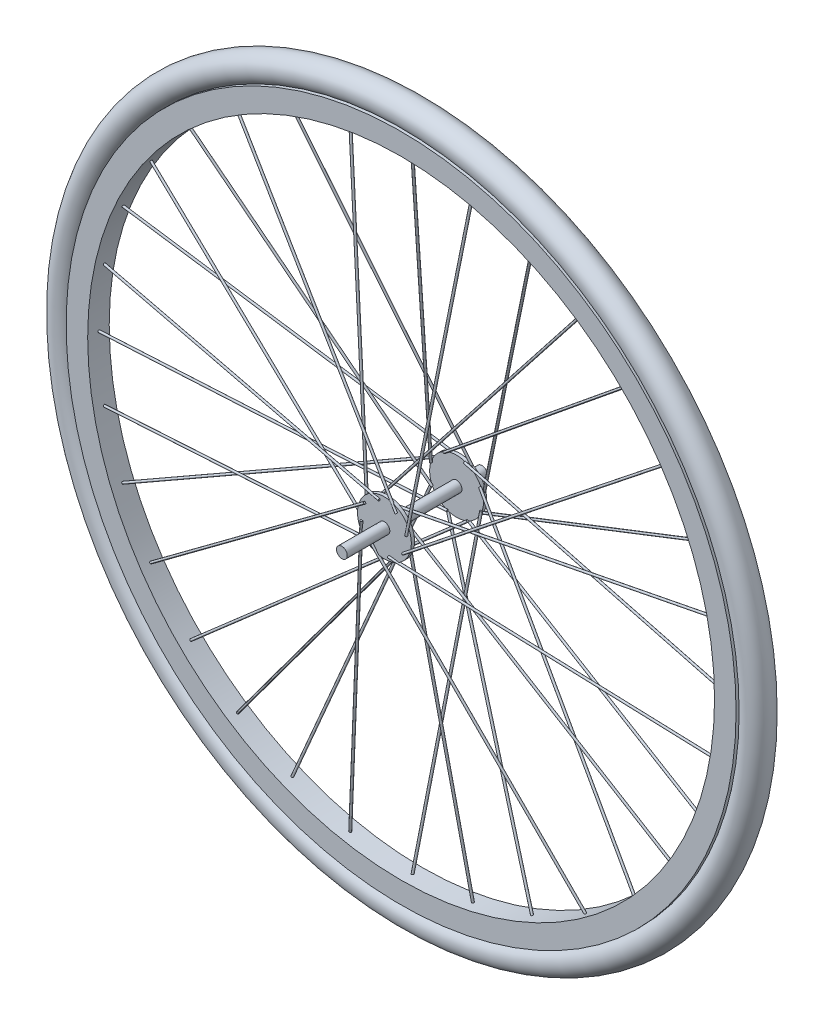
SolidWorks part; units mm, degrees
material "6061-T6 (SS)"
ref_plane "Alzado" through (0, 0, 0) normal (0, 0, 1) x (1, 0, 0)
ref_plane "Planta" through (0, 0, 0) normal (0, 1, 0) x (1, 0, 0)
ref_plane "Vista lateral" through (0, 0, 0) normal (1, 0, 0) x (0, 0, -1)
sketch "Sk_Llanta" plane through (0, 0, 0) normal (0, 0, 1) x (1, 0, 0)
  circle A0 centre (-425.1, 65) radius 311
  circle A1 centre (-425.1, 65) radius 291
  dimension "D1" = 622
  dimension "D2" = 582
extrude "Llanta" add sketch "Sk_Llanta" along normal mid plane 20
sketch "Sk_Cubierta" plane through (0, 0, 0) normal (0, 0, 1) x (1, 0, 0)
  circle A0 centre (-425.1, 65) radius 321.5
  dimension "D1" = 643
sweep "Cubierta" add path "Sk_Cubierta" circular profile diameter 25 parameters "D3"=25
sketch3d "Sk_Eje"
  line L0 (-425.1, 65, -65) -> (-425.1, 65, 65)
  dimension "D1" = 130
sweep "Eje" add path "Sk_Eje" circular profile diameter 10 parameters "D3"=10
sketch3d "Sk_Buje"
  line L0 (-425.1, 65, -50) -> (-425.1, 65, 50)
  dimension "D1" = 100
sweep "Buje" [suppressed] add path "Sk_Buje" circular profile diameter 30 parameters "D3"=30
sketch3d "Sk_Pestana_izq"
  line L0 (-425.1, 65, -44.5) -> (-425.1, 65, -41.5)
  dimension "D1" = 3
sweep "Pestana_izq" add path "Sk_Pestana_izq" circular profile diameter 50 parameters "D3"=50
sketch3d "Sk_Pestana_dcha"
  line L0 (-425.1, 65, 22.5) -> (-425.1, 65, 25.5)
  dimension "D1" = 3
sweep "Pestana_dcha" add path "Sk_Pestana_dcha" circular profile diameter 50 parameters "D3"=50
sketch3d "Sk_Radio_izq_a"
  line L0 (-403.8575, 65.2425, -45) -> (-312.5911, 336.6206, 0)
  dimension "D1" = 289.8286
sweep "Radio_izq_a" add path "Sk_Radio_izq_a" circular profile diameter 2 parameters "D3"=2
sketch3d "Sk_Radio_izq_b"
  line L0 (-402.9187, 75.8162, -41) -> (-217.2106, -142.8894, 0)
  dimension "D1" = 289.8286
sweep "Radio_izq_b" add path "Sk_Radio_izq_b" circular profile diameter 2 parameters "D3"=2
sketch3d "Sk_Radio_dcha_a"
  line L0 (-404.3477, 69.2527, 26) -> (-367.7434, 353.3509, 0)
  dimension "D1" = 287.6241
sweep "Radio_dcha_a" add path "Sk_Radio_dcha_a" circular profile diameter 2 parameters "D3"=2
sketch3d "Sk_Radio_dcha_b"
  line L0 (-408.5094, 75.7967, 22) -> (-180.6479, -98.3376, 0)
  dimension "D1" = 287.6241
sweep "Radio_dcha_b" add path "Sk_Radio_dcha_b" circular profile diameter 2 parameters "D3"=2
ref_axis "Eje_buje" through (-425.1, 65, 25.5) along (0, 0, 1)
sketch3d "Sk_Pinon_1"
  line L0 (-425.1, 65, 26.5) -> (-425.1, 65, 28.5)
  dimension "D1" = 2
sweep "Pinon_1" [suppressed] add path "Sk_Pinon_1" circular profile diameter 120 parameters "D3"=120
sketch "Sk_Dientes_pinon_1" plane through (0, 0, 0) normal (0, 0, 1) x (1, 0, 0)
  line L0 (-367.1, 62.46) -> (-362.1, 64)
  line L1 (-362.1, 64) -> (-362.1, 66)
  line L2 (-362.1, 66) -> (-367.1, 67.54)
  line L3 (-367.1, 67.54) -> (-367.1, 62.46)
extrude "Dientes_pinon_1" [suppressed] add sketch "Sk_Dientes_pinon_1" along normal blind 2 from offset 26.5
pattern_circular "Matriz_Dientes_pinon_1" [suppressed] count 30 over 360 about axis through (-425.1, 65, 25.5) along (0, 0, 1) of bodies 111
sketch3d "Sk_Pinon_2"
  line L0 (-425.1, 65, 30.5) -> (-425.1, 65, 32.5)
  dimension "D1" = 2
sweep "Pinon_2" [suppressed] add path "Sk_Pinon_2" circular profile diameter 110 parameters "D3"=110
sketch "Sk_Dientes_pinon_2" plane through (0, 0, 0) normal (0, 0, 1) x (1, 0, 0)
  line L0 (-372.1, 62.46) -> (-367.1, 64)
  line L1 (-367.1, 64) -> (-367.1, 66)
  line L2 (-367.1, 66) -> (-372.1, 67.54)
  line L3 (-372.1, 67.54) -> (-372.1, 62.46)
extrude "Dientes_pinon_2" [suppressed] add sketch "Sk_Dientes_pinon_2" along normal blind 2 from offset 30.5
pattern_circular "Matriz_Dientes_pinon_2" [suppressed] count 27 over 360 about axis through (-425.1, 65, 25.5) along (0, 0, 1) of bodies 111
sketch3d "Sk_Pinon_3"
  line L0 (-425.1, 65, 34.5) -> (-425.1, 65, 36.5)
  dimension "D1" = 2
sweep "Pinon_3" [suppressed] add path "Sk_Pinon_3" circular profile diameter 100 parameters "D3"=100
sketch "Sk_Dientes_pinon_3" plane through (0, 0, 0) normal (0, 0, 1) x (1, 0, 0)
  line L0 (-377.1, 62.46) -> (-372.1, 64)
  line L1 (-372.1, 64) -> (-372.1, 66)
  line L2 (-372.1, 66) -> (-377.1, 67.54)
  line L3 (-377.1, 67.54) -> (-377.1, 62.46)
extrude "Dientes_pinon_3" [suppressed] add sketch "Sk_Dientes_pinon_3" along normal blind 2 from offset 34.5
pattern_circular "Matriz_Dientes_pinon_3" [suppressed] count 25 over 360 about axis through (-425.1, 65, 25.5) along (0, 0, 1) of bodies 111
sketch3d "Sk_Pinon_4"
  line L0 (-425.1, 65, 38.5) -> (-425.1, 65, 40.5)
  dimension "D1" = 2
sweep "Pinon_4" [suppressed] add path "Sk_Pinon_4" circular profile diameter 90 parameters "D3"=90
sketch "Sk_Dientes_pinon_4" plane through (0, 0, 0) normal (0, 0, 1) x (1, 0, 0)
  line L0 (-382.1, 62.46) -> (-377.1, 64)
  line L1 (-377.1, 64) -> (-377.1, 66)
  line L2 (-377.1, 66) -> (-382.1, 67.54)
  line L3 (-382.1, 67.54) -> (-382.1, 62.46)
extrude "Dientes_pinon_4" [suppressed] add sketch "Sk_Dientes_pinon_4" along normal blind 2 from offset 38.5
pattern_circular "Matriz_Dientes_pinon_4" [suppressed] count 22 over 360 about axis through (-425.1, 65, 25.5) along (0, 0, 1) of bodies 111
sketch3d "Sk_Pinon_5"
  line L0 (-425.1, 65, 42.5) -> (-425.1, 65, 44.5)
  dimension "D1" = 2
sweep "Pinon_5" [suppressed] add path "Sk_Pinon_5" circular profile diameter 82 parameters "D3"=82
sketch "Sk_Dientes_pinon_5" plane through (0, 0, 0) normal (0, 0, 1) x (1, 0, 0)
  line L0 (-386.1, 62.46) -> (-381.1, 64)
  line L1 (-381.1, 64) -> (-381.1, 66)
  line L2 (-381.1, 66) -> (-386.1, 67.54)
  line L3 (-386.1, 67.54) -> (-386.1, 62.46)
extrude "Dientes_pinon_5" [suppressed] add sketch "Sk_Dientes_pinon_5" along normal blind 2 from offset 42.5
pattern_circular "Matriz_Dientes_pinon_5" [suppressed] count 20 over 360 about axis through (-425.1, 65, 25.5) along (0, 0, 1) of bodies 111
sketch3d "Sk_Pinon_6"
  line L0 (-425.1, 65, 46.5) -> (-425.1, 65, 48.5)
  dimension "D1" = 2
sweep "Pinon_6" [suppressed] add path "Sk_Pinon_6" circular profile diameter 74 parameters "D3"=74
sketch "Sk_Dientes_pinon_6" plane through (0, 0, 0) normal (0, 0, 1) x (1, 0, 0)
  line L0 (-390.1, 62.46) -> (-385.1, 64)
  line L1 (-385.1, 64) -> (-385.1, 66)
  line L2 (-385.1, 66) -> (-390.1, 67.54)
  line L3 (-390.1, 67.54) -> (-390.1, 62.46)
extrude "Dientes_pinon_6" [suppressed] add sketch "Sk_Dientes_pinon_6" along normal blind 2 from offset 46.5
pattern_circular "Matriz_Dientes_pinon_6" [suppressed] count 18 over 360 about axis through (-425.1, 65, 25.5) along (0, 0, 1) of bodies 111
sketch3d "Sk_Pinon_7"
  line L0 (-425.1, 65, 50.5) -> (-425.1, 65, 52.5)
  dimension "D1" = 2
sweep "Pinon_7" [suppressed] add path "Sk_Pinon_7" circular profile diameter 66 parameters "D3"=66
sketch "Sk_Dientes_pinon_7" plane through (0, 0, 0) normal (0, 0, 1) x (1, 0, 0)
  line L0 (-394.1, 62.46) -> (-389.1, 64)
  line L1 (-389.1, 64) -> (-389.1, 66)
  line L2 (-389.1, 66) -> (-394.1, 67.54)
  line L3 (-394.1, 67.54) -> (-394.1, 62.46)
extrude "Dientes_pinon_7" [suppressed] add sketch "Sk_Dientes_pinon_7" along normal blind 2 from offset 50.5
pattern_circular "Matriz_Dientes_pinon_7" [suppressed] count 16 over 360 about axis through (-425.1, 65, 25.5) along (0, 0, 1) of bodies 111
sketch3d "Sk_Pinon_8"
  line L0 (-425.1, 65, 54.5) -> (-425.1, 65, 56.5)
  dimension "D1" = 2
sweep "Pinon_8" [suppressed] add path "Sk_Pinon_8" circular profile diameter 58 parameters "D3"=58
sketch "Sk_Dientes_pinon_8" plane through (0, 0, 0) normal (0, 0, 1) x (1, 0, 0)
  line L0 (-398.1, 62.46) -> (-393.1, 64)
  line L1 (-393.1, 64) -> (-393.1, 66)
  line L2 (-393.1, 66) -> (-398.1, 67.54)
  line L3 (-398.1, 67.54) -> (-398.1, 62.46)
extrude "Dientes_pinon_8" [suppressed] add sketch "Sk_Dientes_pinon_8" along normal blind 2 from offset 54.5
pattern_circular "Matriz_Dientes_pinon_8" [suppressed] count 14 over 360 about axis through (-425.1, 65, 25.5) along (0, 0, 1) of bodies 111
pattern_circular "Matriz_radios" count 8 over 360 about axis through (-425.1, 65, 25.5) along (0, 0, 1) of "Eje"
